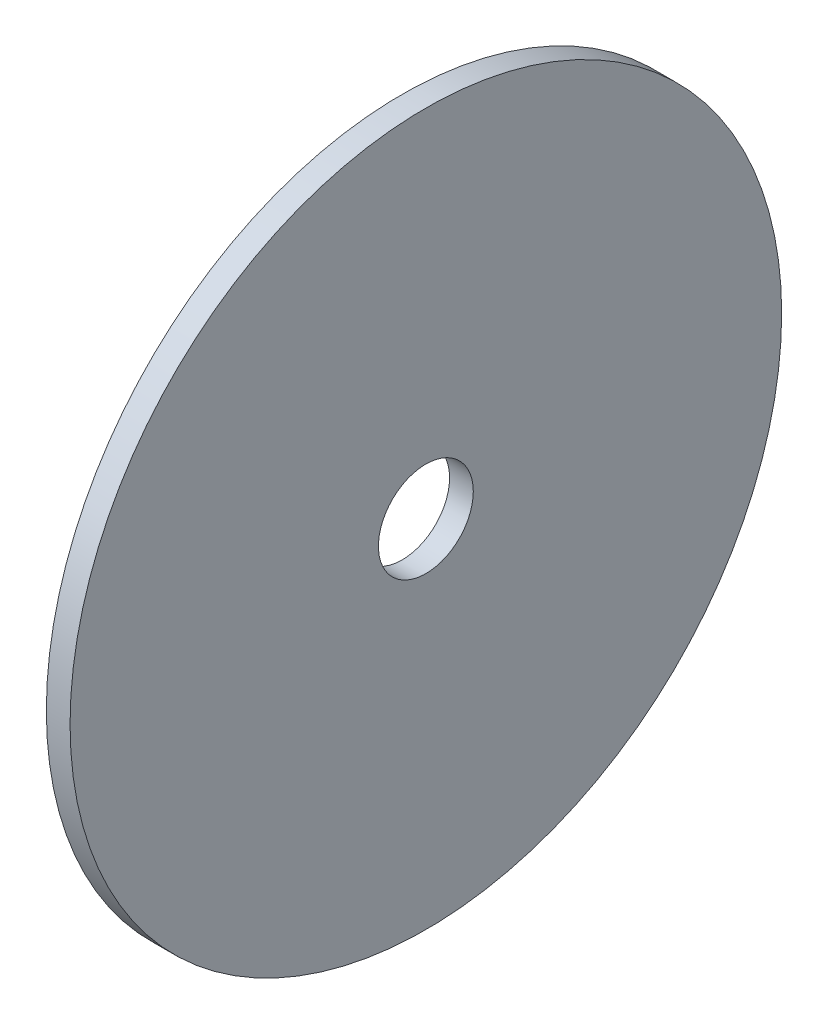
SolidWorks part; units mm, degrees
ref_plane "Alzado" through (0, 0, 0) normal (0, 0, 1) x (1, 0, 0)
ref_plane "Planta" through (0, 0, 0) normal (0, 1, 0) x (1, 0, 0)
ref_plane "Vista lateral" through (0, 0, 0) normal (1, 0, 0) x (0, 0, -1)
sketch "Croquis1" plane through (0, 0, 0) normal (1, 0, 0) x (0, 0, -1)
  circle A0 centre (0, 0) radius 15
  circle A1 centre (0, 0) radius 2
  dimension "D1" = 4
  dimension "D2" = 30
extrude "Saliente-Extruir1" add sketch "Croquis1" along normal blind 1
